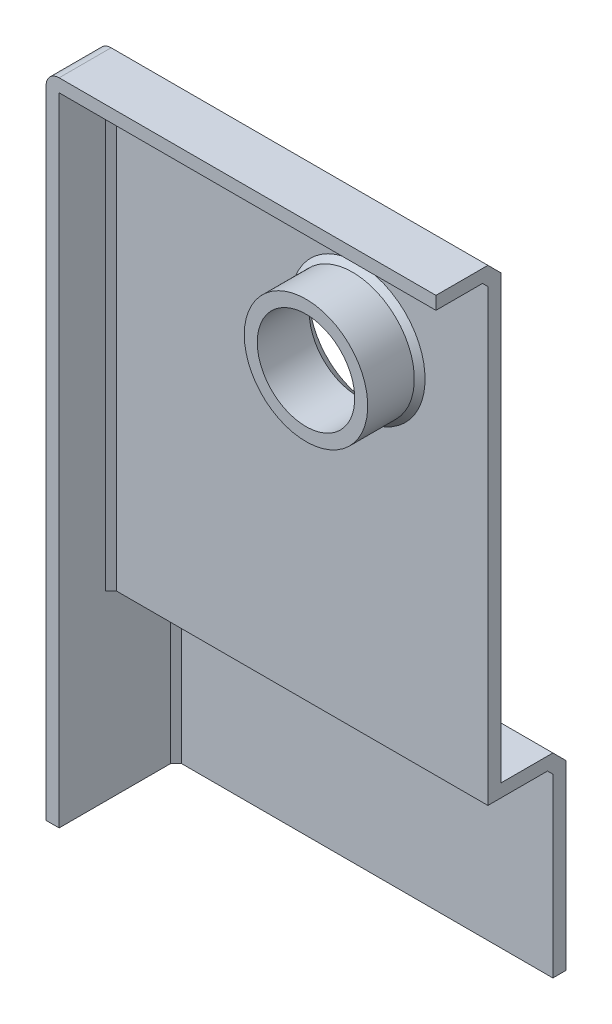
SolidWorks part; units mm, degrees
material "1060 Alloy"
ref_plane "Front Plane" through (0, 0, 0) normal (0, 0, 1) x (1, 0, 0)
ref_plane "Top Plane" through (0, 0, 0) normal (0, 1, 0) x (1, 0, 0)
ref_plane "Right Plane" through (0, 0, 0) normal (1, 0, 0) x (0, 0, -1)
sketch "Sketch1" plane through (0, 0, 0) normal (0, 0, 1) x (1, 0, 0)
  line L1 (0, 0) -> (76.2, 0)
  line L2 (0, 0) -> (0, 127)
  line L3 (0, 127) -> (76.2, 127)
  line L4 (76.2, 0) -> (76.2, 127)
  dimension "D1" = 76.2
  dimension "5" = 127
extrude "Boss-Extrude2" add sketch "Sketch1" along normal blind 12.7
sketch "Sketch2" plane through (0, 0, 0) normal (0, 0, -1) x (-1, 0, 0)
  line L0 (0, 127) -> (0, 0) construction
  line L1 (-76.2, 0) -> (0, 0)
  line L2 (-76.2, 0) -> (-76.2, 38.1)
  line L3 (-76.2, 38.1) -> (0, 38.1)
  line L4 (0, 0) -> (0, 38.1)
  dimension "D1" = 38.1
extrude "Boss-Extrude3" add sketch "Sketch2" along normal blind 12.7
sketch "Sketch4" plane through (0, 0, 0) normal (0, 0, -1) x (-1, 0, 0)
  line L0 (-76.2, 38.1) -> (-76.2, 127) construction
  line L1 (-76.2, 127) -> (0, 127) construction
  circle A0 centre (-50.8, 101.6) radius 9.525
  dimension "D1" = 25.4
  dimension "D2" = 19.05
  dimension "D3" = 25.4
extrude "Cut-Extrude1" cut sketch "Sketch4" against normal through all
fillet "Fillet1" radius 2.54 2 edges at (0, 38.1, -6.35) (0, 127, 6.35)
chamfer "Chamfer1" distance 2.54 angle 45 7 edges at (41.275, 101.6, 0) (0, 80.01, 0) (0.7439, 126.2561, 0) (39.37, 127, 0) (0, 17.78, -12.7) (0.7439, 37.3561, -12.7) (39.37, 38.1, -12.7)
shell "Shell1" thickness 2.54 removed face at (76.2, 61.2775, -0.9525) removed face at (30.988, 0, -2.032) removed face at (41.275, 101.6, 12.7)
